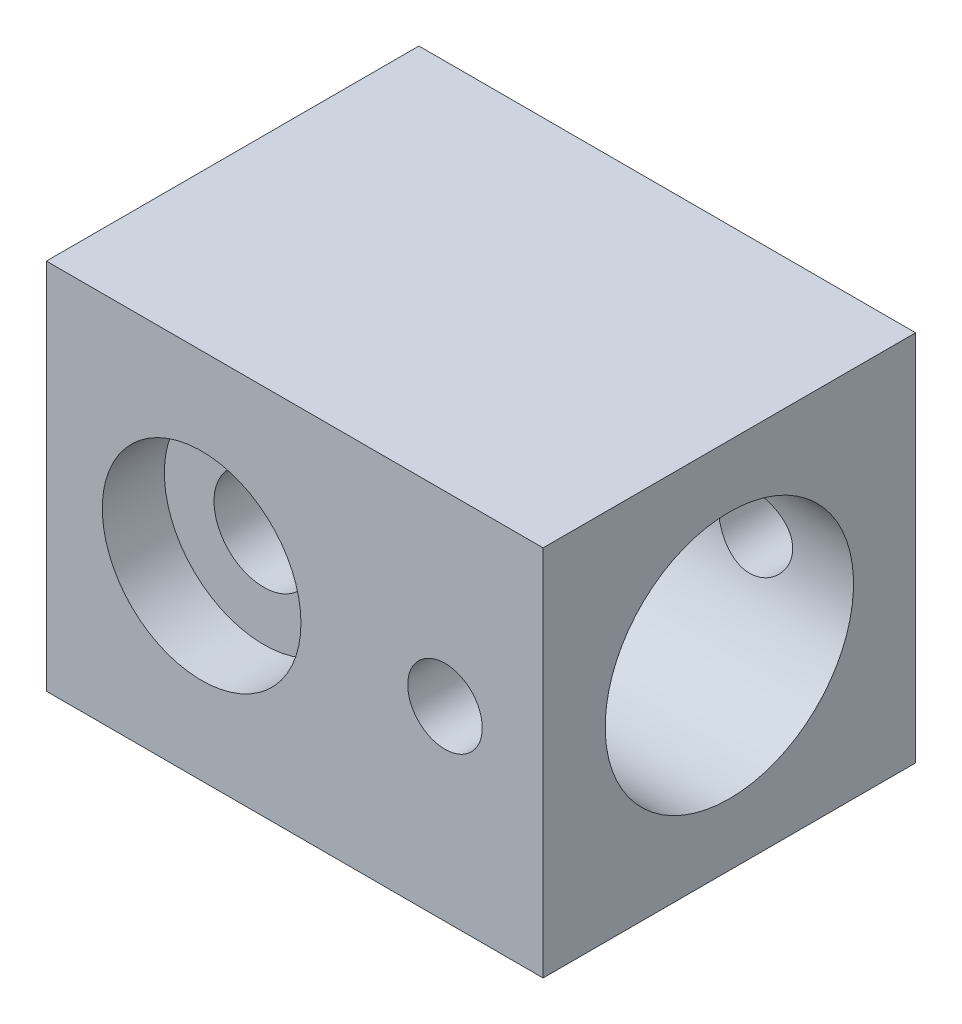
SolidWorks part; units mm, degrees
material "6061-T6 (SS)"
ref_plane "Front Plane" through (0, 0, 0) normal (0, 0, 1) x (1, 0, 0)
ref_plane "Top Plane" through (0, 0, 0) normal (0, 1, 0) x (1, 0, 0)
ref_plane "Right Plane" through (0, 0, 0) normal (1, 0, 0) x (0, 0, -1)
sketch "Sketch9" plane through (0, 0, 0) normal (0, 0, 1) x (1, 0, 0)
  line L1 (0, 0) -> (40, 0)
  line L2 (0, 0) -> (0, -30)
  line L3 (0, -30) -> (40, -30)
  line L4 (40, 0) -> (40, -30)
  dimension "D1" = 30
  dimension "D2" = 40
extrude "Boss-Extrude2" add sketch "Sketch9" along normal blind 30
sketch "Sketch10" plane through (40, 0, 0) normal (1, 0, 0) x (0, 0, -1)
  line L0 (-30, -30) -> (0, 0) construction
  circle A0 centre (-15, -15) radius 10
  dimension "D1" = 20
extrude "Cut-Extrude1" cut sketch "Sketch10" against normal blind 15
sketch "Sketch11" plane through (0, 0, 30) normal (0, 0, 1) x (1, 0, 0)
  line L0 (0, 0) -> (25, -30) construction
  line L1 (0, -30) -> (40, -30) construction
  circle A0 centre (12.5, -15) radius 8
  circle A1 centre (12.5, -15) radius 4
  dimension "D2" = 16
  dimension "D3" = 8
  dimension "D1" = 25
extrude "Cut-Extrude2" cut sketch "Sketch11" against normal blind 5 contours A1 L0 | L0 A1 | A0 region at (13.8042, -13.9132, 30) region at (11.1958, -16.0868, 30)
extrude "Cut-Extrude3" cut sketch "Sketch11<3>" against normal blind 101 contours L0 A1 | A1 L0 region at (13.8042, -13.9132, 30) region at (11.1958, -16.0868, 30)
sketch "Sketch11<3>" plane through (0, 0, 30) normal (0, 0, 1) x (1, 0, 0) same geometry as "Sketch11"
sketch "Sketch12" plane through (0, 0, 30) normal (0, 0, 1) x (1, 0, 0)
  line L0 (40, -30) -> (40, 0) construction
  circle A0 centre (32.1, -15) radius 3
  dimension "D1" = 6
  dimension "D2" = 7.9
extrude "Cut-Extrude4" cut sketch "Sketch12" against normal blind 101
ref_plane "Plane1" through (0, 0, 15) normal (0, 0, -1) x (-1, 0, 0)
mirror "Mirror1" about plane through (0, 0, 15) normal (0, 0, -1) of "Cut-Extrude2"
